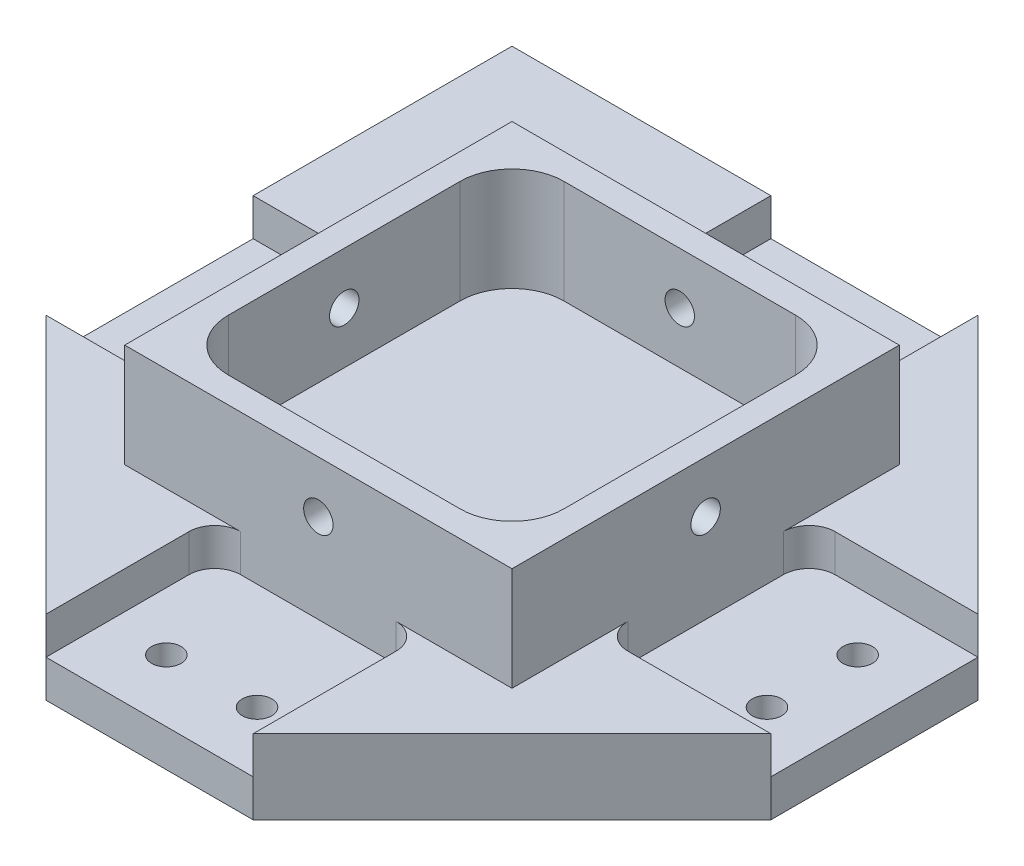
SolidWorks part; units mm, degrees
material "6061 Alloy"
ref_plane "Front Plane" through (0, 0, 0) normal (0, 0, 1) x (1, 0, 0)
ref_plane "Top Plane" through (0, 0, 0) normal (0, 1, 0) x (1, 0, 0)
ref_plane "Right Plane" through (0, 0, 0) normal (1, 0, 0) x (0, 0, -1)
sketch "Sketch1" plane through (0, 0, 0) normal (0, 1, 0) x (1, 0, 0)
  line L1 (0, 0) -> (88.9, 0)
  line L2 (0, 0) -> (0, 88.9)
  line L3 (0, 88.9) -> (88.9, 88.9)
  line L4 (88.9, 0) -> (88.9, 88.9)
  dimension "D1" = 88.9
  dimension "D2" = 88.9
extrude "Boss-Extrude1" add sketch "Sketch1" along normal blind 9.144
sketch "Sketch2" plane through (0, 9.144, 0) normal (0, 1, 0) x (1, 0, 0)
  line L0 (88.9, 88.9) -> (0, 88.9) construction
  line L1 (31.75, 88.9) -> (57.15, 88.9)
  line L2 (31.75, 88.9) -> (31.75, 67.31)
  line L3 (31.75, 67.31) -> (57.15, 67.31)
  line L4 (57.15, 88.9) -> (57.15, 67.31)
  line L5 (0, 88.9) -> (0, 0) construction
  line L6 (0, 57.15) -> (21.59, 57.15)
  line L7 (0, 57.15) -> (0, 31.75)
  line L8 (0, 31.75) -> (21.59, 31.75)
  line L9 (21.59, 57.15) -> (21.59, 31.75)
  line L10 (0, 0) -> (88.9, 0) construction
  line L11 (31.75, 0) -> (57.15, 0)
  line L12 (31.75, 0) -> (31.75, 21.59)
  line L13 (31.75, 21.59) -> (57.15, 21.59)
  line L14 (57.15, 0) -> (57.15, 21.59)
  line L15 (88.9, 0) -> (88.9, 88.9) construction
  line L16 (88.9, 57.15) -> (67.31, 57.15)
  line L17 (88.9, 57.15) -> (88.9, 31.75)
  line L18 (88.9, 31.75) -> (67.31, 31.75)
  line L19 (67.31, 57.15) -> (67.31, 31.75)
  dimension "D1" = 31.75
  dimension "D2" = 25.4
  dimension "D3" = 25.4
  dimension "D4" = 31.75
  dimension "D5" = 25.4
  dimension "D6" = 31.75
  dimension "D7" = 25.4
  dimension "D8" = 31.75
  dimension "D9" = 21.59
  dimension "D10" = 21.59
  dimension "D11" = 21.59
  dimension "D12" = 21.59
extrude "Cut-Extrude1" cut sketch "Sketch2" against normal blind 4.572
sketch "Sketch3" plane through (0, 9.144, 0) normal (0, 1, 0) x (1, 0, 0)
  line L0 (31.75, 88.9) -> (0, 88.9) construction
  line L1 (20.6375, 68.2625) -> (68.2625, 68.2625)
  line L2 (20.6375, 68.2625) -> (20.6375, 20.6375)
  line L3 (20.6375, 20.6375) -> (68.2625, 20.6375)
  line L4 (68.2625, 68.2625) -> (68.2625, 20.6375)
  line L5 (0, 31.75) -> (0, 0) construction
  line L6 (88.9, 31.75) -> (88.9, 57.15) construction
  line L7 (57.15, 88.9) -> (31.75, 88.9) construction
  line L8 (0, 57.15) -> (0, 31.75) construction
  line L9 (31.75, 0) -> (57.15, 0) construction
  circle A0 centre (28.194, 44.45) radius 2.4
  circle A1 centre (44.45, 60.706) radius 2.4
  circle A2 centre (60.706, 44.45) radius 2.4
  circle A3 centre (44.45, 28.194) radius 2.4
  dimension "D5" = 4.8
  dimension "D6" = 4.8
  dimension "D7" = 4.8
  dimension "D8" = 4.8
  dimension "D1" = 47.625
  dimension "D2" = 47.625
  dimension "D3" = 20.6375
  dimension "D4" = 20.6375
  dimension "D9" = 28.194
  dimension "D10" = 28.194
  dimension "D11" = 28.194
  dimension "D12" = 28.194
  dimension "D13" = 23.8125
  dimension "D14" = 23.8125
  dimension "D15" = 23.8125
  dimension "D16" = 23.8125
extrude "Cut-Extrude2" [suppressed] cut sketch "Sketch3" against normal through all contours A2 | A1 | A0 | A3
sketch "Sketch4" plane through (0, 4.572, 0) normal (0, 1, 0) x (1, 0, 0)
  line L0 (0, 57.15) -> (0, 31.75) construction
  line L1 (57.15, 88.9) -> (31.75, 88.9) construction
  line L2 (88.9, 31.75) -> (88.9, 57.15) construction
  line L3 (31.75, 0) -> (57.15, 0) construction
  line L4 (0, 31.75) -> (21.59, 31.75) construction
  line L5 (31.75, 21.59) -> (31.75, 0) construction
  line L6 (67.31, 31.75) -> (88.9, 31.75) construction
  line L7 (57.15, 67.31) -> (57.15, 88.9) construction
  circle A0 centre (81.28, 50.0126) radius 1.8034
  circle A1 centre (81.28, 38.8874) radius 1.8034
  circle A2 centre (50.0126, 81.28) radius 1.8034
  circle A3 centre (38.8874, 81.28) radius 1.8034
  circle A4 centre (7.62, 50.0126) radius 1.8034
  circle A5 centre (7.62, 38.8874) radius 1.8034
  circle A6 centre (38.8874, 7.62) radius 1.8034
  circle A7 centre (50.0126, 7.62) radius 1.8034
  dimension "D1" = 3.6068
  dimension "D2" = 3.6068
  dimension "D3" = 3.6068
  dimension "D4" = 3.6068
  dimension "D5" = 3.6068
  dimension "D6" = 3.6068
  dimension "D7" = 3.6068
  dimension "D8" = 3.6068
  dimension "D9" = 7.62
  dimension "D10" = 7.62
  dimension "D11" = 7.62
  dimension "D12" = 7.62
  dimension "D13" = 7.62
  dimension "D14" = 7.62
  dimension ".313" = 7.62
  dimension "D16" = 7.62
  dimension "D17" = 11.1252
  dimension "D18" = 7.1374
  dimension "D19" = 7.1374
  dimension "D20" = 11.1252
  dimension "D21" = 7.1374
  dimension "D22" = 11.1252
  dimension "D23" = 7.1374
  dimension "D24" = 11.1252
extrude "Cut-Extrude3" cut sketch "Sketch4" against normal through all
sketch "Sketch5" plane through (0, 9.144, 0) normal (0, 1, 0) x (1, 0, 0)
  line L0 (88.9, 88.9) -> (57.15, 88.9) construction
  line L1 (88.9, 31.75) -> (88.9, 57.15) construction
  circle A0 centre (44.45, 44.45) radius 6.35
  dimension "D1" = 12.7
  dimension "D2" = 44.45
  dimension "D3" = 44.45
extrude "Cut-Extrude4" [suppressed] cut sketch "Sketch5" against normal through all
sketch "Sketch6" plane through (0, 9.144, 0) normal (0, 1, 0) x (1, 0, 0)
  line L0 (88.9, 31.75) -> (57.15, 0)
  line L1 (57.15, 0) -> (88.9, 0)
  line L2 (88.9, 0) -> (88.9, 31.75)
extrude "Cut-Extrude5" cut sketch "Sketch6" against normal through all
sketch "Sketch7" plane through (0, 9.144, 0) normal (0, 1, 0) x (1, 0, 0)
  line L0 (0, 88.9) -> (0, 57.15) construction
  line L1 (20.701, 68.199) -> (68.199, 68.199)
  line L2 (20.701, 68.199) -> (20.701, 20.701)
  line L3 (20.701, 20.701) -> (68.199, 20.701)
  line L4 (68.199, 68.199) -> (68.199, 20.701)
  line L5 (0, 0) -> (31.75, 0) construction
  line L7 (23.876, 23.876) -> (65.024, 23.876)
  line L8 (23.876, 23.876) -> (23.876, 65.024)
  line L9 (23.876, 65.024) -> (65.024, 65.024)
  line L10 (65.024, 23.876) -> (65.024, 65.024)
  dimension "D1" = 47.498
  dimension "D2" = 47.498
  dimension "D3" = 20.701
  dimension "D4" = 20.701
  dimension "D5" = 3.175
  dimension "D6" = 3.175
  dimension "D7" = 3.175
  dimension "D8" = 3.175
extrude "Boss-Extrude2" add sketch "Sketch7" along normal blind 12.7 and the other way up to next (4.572 mm away)
fillet "Fillet9" radius 6.35 1 edges at (65.024, 15.494, -23.876)
fillet "Fillet10" radius 6.35 1 edges at (23.876, 15.494, -23.876)
fillet "Fillet11" radius 6.35 1 edges at (65.024, 15.494, -65.024)
fillet "Fillet12" radius 6.35 1 edges at (23.876, 15.494, -65.024)
fillet "Fillet15" radius 3.175 1 edges at (20.701, 6.858, -57.15)
fillet "Fillet16" radius 3.175 1 edges at (31.75, 6.858, -20.701)
fillet "Fillet17" radius 3.175 1 edges at (57.15, 6.858, -20.701)
fillet "Fillet18" radius 3.175 1 edges at (68.199, 6.858, -57.15)
fillet "Fillet19" radius 3.175 1 edges at (68.199, 6.858, -31.75)
fillet "Fillet20" radius 3.175 1 edges at (31.75, 6.858, -68.199)
fillet "Fillet21" radius 3.175 1 edges at (57.15, 6.858, -68.199)
fillet "Fillet22" radius 3.175 1 edges at (20.701, 6.858, -31.75)
sketch "Sketch9" plane through (0, 0, -68.199) normal (0, 0, -1) x (-1, 0, 0)
  line L0 (-68.199, 21.844) -> (-68.199, 9.144) construction
  line L1 (-68.199, 21.844) -> (-20.701, 21.844) construction
  circle A0 centre (-44.45, 15.494) radius 1.8034
  dimension "D1" = 3.6068
  dimension "D2" = 23.749
  dimension "D3" = 6.35
extrude "Cut-Extrude6" cut sketch "Sketch9" against normal through all
sketch "Sketch10" plane through (68.199, 0, 0) normal (1, 0, 0) x (0, 0, -1)
  line L0 (20.701, 21.844) -> (68.199, 21.844) construction
  line L1 (20.701, 21.844) -> (20.701, 9.144) construction
  circle A0 centre (44.45, 15.494) radius 1.8034
  dimension "D1" = 3.6068
  dimension "D2" = 6.35
  dimension "D3" = 23.749
extrude "Cut-Extrude7" cut sketch "Sketch10" against normal through all
sketch "Sketch12" plane through (0, 9.144, 0) normal (0, 1, 0) x (1, 0, 0)
  line L0 (0, 31.75) -> (31.75, 0)
  line L1 (31.75, 0) -> (0, 0)
  line L2 (0, 0) -> (0, 31.75)
  line L3 (57.15, 88.9) -> (88.9, 57.15)
  line L4 (88.9, 57.15) -> (88.9, 88.9)
  line L5 (88.9, 88.9) -> (57.15, 88.9)
sketch "Sketch14" plane through (0, 0, 0) normal (0, -1, 0) x (1, 0, 0)
  line L1 (0, -88.9) -> (0, 0) construction
  line L3 (0, 0) -> (57.15, 0) construction
  circle A0 centre (27.9855, -27.906) radius 2.5797
  circle A1 centre (59.4164, -59.3369) radius 2.5797
  dimension "D1" = 44.45
  dimension "D2" = 5.1594
  dimension "D3" = 5.1594
  dimension "D4" = 27.9855
  dimension "D6" = 27.906
extrude "Cut-Extrude9" cut sketch "Sketch14" against normal through all
extrude "Cut-Extrude10" cut sketch "Sketch12" against normal through all
equation "\"hinge_hole\"= 0.142in"
equation "\"D1@Sketch4\"=\"hinge_hole\""
equation "\"D2@Sketch4\"=\"hinge_hole\""
equation "\"D3@Sketch4\"=\"hinge_hole\""
equation "\"D4@Sketch4\"=\"hinge_hole\""
equation "\"D5@Sketch4\"=\"hinge_hole\""
equation "\"D6@Sketch4\"=\"hinge_hole\""
equation "\"D7@Sketch4\"=\"hinge_hole\""
equation "\"D8@Sketch4\"=\"hinge_hole\""
equation "\"hinge_hole_dist\"= 0.297 + 0.25"
equation "\".313@Sketch4\"=.3"
equation "\"hinge_hole_sep\"=0.438"
equation "\"hinge_hole_from_wall\"= ( 1 - \"hinge_hole_sep\" ) / 2"
equation "\"D17@Sketch4\"=\"hinge_hole_sep\""
equation "\"D18@Sketch4\"=\"hinge_hole_from_wall\""
equation "\"D19@Sketch4\"=\"hinge_hole_from_wall\""
equation "\"D20@Sketch4\"=\"hinge_hole_sep\""
equation "\"D21@Sketch4\"=\"hinge_hole_from_wall\""
equation "\"D22@Sketch4\"=\"hinge_hole_sep\""
equation "\"D23@Sketch4\"=\"hinge_hole_from_wall\""
equation "\"D24@Sketch4\"=\"hinge_hole_sep\""
equation "\"D9@Sketch2\"=\"hinge_hole_dist\" + (0.6-0.297)"
equation "\"D12@Sketch2\"=\"hinge_hole_dist\" + (0.6-0.297)"
equation "\"D11@Sketch2\"=\"hinge_hole_dist\" + (0.6-0.297)"
equation "\"D10@Sketch2\"=\"hinge_hole_dist\" + (0.6-0.297)"
